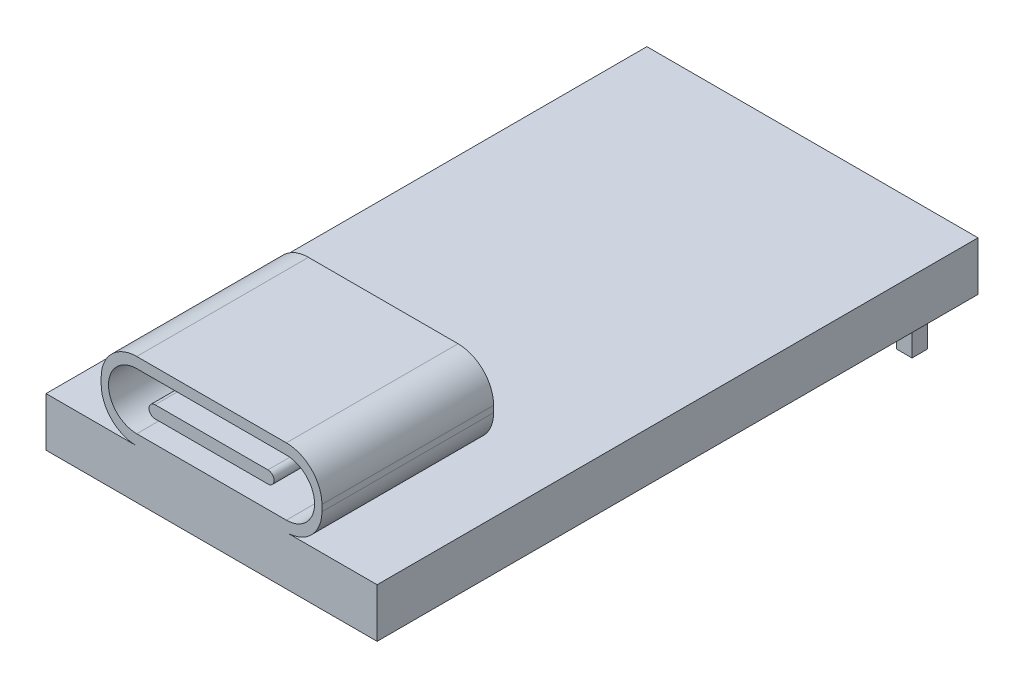
SolidWorks part; units mm, degrees
ref_plane "Front Plane" through (0, 0, 0) normal (0, 0, 1) x (1, 0, 0)
ref_plane "Top Plane" through (0, 0, 0) normal (0, 1, 0) x (1, 0, 0)
ref_plane "Right Plane" through (0, 0, 0) normal (1, 0, 0) x (0, 0, -1)
sketch "Sketch1" plane through (0, 0, 0) normal (0, 1, 0) x (1, 0, 0)
  line L1 (0, 0) -> (13.5, 0)
  line L2 (0, 0) -> (0, 24.5)
  line L3 (0, 24.5) -> (13.5, 24.5)
  line L4 (13.5, 0) -> (13.5, 24.5)
  dimension "D1" = 13.5
  dimension "D2" = 24.5
extrude "Boss-Extrude1" add sketch "Sketch1" along normal blind 2
sketch "Sketch2" plane through (0, 2, 0) normal (0, 1, 0) x (1, 0, 0)
  line L0 (0, 0) -> (13.5, 0) construction
  line L1 (2.25, 0) -> (11.25, 0)
  line L2 (2.25, 0) -> (2.25, 7)
  line L3 (2.25, 7) -> (11.25, 7)
  line L4 (11.25, 0) -> (11.25, 7)
  line L5 (11.25, 3.5) -> (13.5, 3.5) construction
  line L6 (13.5, 0) -> (13.5, 24.5) construction
  line L7 (2.25, 3.5) -> (0, 3.5) construction
  line L8 (0, 24.5) -> (0, 0) construction
  dimension "D1" = 9
  dimension "D2" = 7
extrude "Boss-Extrude2" add sketch "Sketch2" along normal blind 3.16
sketch "Sketch3" plane through (0, 0, 0) normal (0, 0, 1) x (1, 0, 0)
  line L0 (6.75, 5.16) -> (6.75, 3.58) construction
  line L1 (2.25, 5.16) -> (11.25, 5.16) construction
  line L2 (6.75, 3.58) -> (6.75, 2) construction
  line L3 (6.75, 2) -> (9.8, 2)
  line L4 (6.75, 2) -> (3.7, 2)
  line L5 (2.25, 3.45) -> (2.25, 3.71)
  line L6 (2.25, 5.16) -> (2.25, 2) construction
  line L7 (3.7, 5.16) -> (9.8, 5.16)
  line L8 (11.25, 3.71) -> (11.25, 3.45)
  line L9 (9.8, 5.16) -> (11.25, 5.16)
  line L10 (11.25, 5.16) -> (11.25, 3.71)
  line L11 (11.25, 3.45) -> (11.25, 2)
  line L12 (11.25, 2) -> (9.8, 2)
  line L13 (3.7, 2) -> (2.25, 2)
  line L14 (2.25, 2) -> (2.25, 3.45)
  line L15 (2.25, 3.71) -> (2.25, 5.16)
  line L16 (2.25, 5.16) -> (3.7, 5.16)
  arc A0 (11.25, 3.71) -> (9.8, 5.16) centre (9.8, 3.71) ccw
  arc A1 (11.25, 3.45) -> (9.8, 2) centre (9.8, 3.45) cw
  arc A2 (2.25, 3.45) -> (3.7, 2) centre (3.7, 3.45) ccw
  arc A3 (2.25, 3.71) -> (3.7, 5.16) centre (3.7, 3.71) cw
  point P18 (11.25, 5.16)
  point P25 (2.25, 5.16)
  line M6 (11.25, 2) -> (11.25, 5.16)
  line M7 (11.25, 5.16) -> (2.25, 5.16)
  line M8 (2.25, 5.16) -> (2.25, 2)
  dimension "D2" = 1.45
  dimension "D1" = 1.58
extrude "Cut-Extrude1" cut sketch "Sketch3" against normal blind 7.16 contours A2 L13 M8 | A3 M8 M7 | A0 M6 M7 | A1 L12 M6 region at (10.9261, 2.3239, 0) region at (2.5739, 2.3239, 0) region at (10.9261, 4.8361, 0) region at (2.5739, 4.8361, 0)
sketch "Sketch4" plane through (0, 0, 0) normal (0, 0, 1) x (1, 0, 0)
  line L0 (3.7, 5.16) -> (3.7, 2) construction
  line L1 (9.8, 5.16) -> (9.8, 2) construction
  line L2 (3.7, 3.58) -> (9.8, 3.58) construction
  line L3 (3.7, 3.83) -> (9.8, 3.83)
  line L4 (3.7, 3.33) -> (9.8, 3.33)
  line L5 (3.7, 3.58) -> (9.8, 3.58) construction
  line L6 (3.7, 4.73) -> (9.8, 4.73)
  line L7 (3.7, 2.43) -> (9.8, 2.43)
  arc A0 (3.7, 3.83) -> (3.7, 3.33) centre (3.7, 3.58) ccw
  arc A1 (9.8, 3.33) -> (9.8, 3.83) centre (9.8, 3.58) ccw
  arc A2 (3.7, 4.73) -> (3.7, 2.43) centre (3.7, 3.58) ccw
  arc A3 (9.8, 2.43) -> (9.8, 4.73) centre (9.8, 3.58) ccw
  point P7 (6.75, 3.58)
  point P17 (6.75, 3.58)
  dimension "D1" = 0.5
  dimension "D2" = 2.3
extrude "Cut-Extrude2" cut sketch "Sketch4" against normal blind 2.16
sketch "Sketch5" plane through (0, 0, 0) normal (0, 0, 1) x (1, 0, 0)
  line L0 (3.45, 3.58) -> (4.45, 3.58) construction
  line L1 (10.05, 3.58) -> (9.05, 3.58) construction
  line L2 (4.45, 3.58) -> (9.05, 3.58) construction
  line L3 (4.45, 3.83) -> (9.05, 3.83)
  line L4 (4.45, 3.33) -> (9.05, 3.33)
  line L6 (9.8, 3.83) -> (3.7, 3.83) construction
  line L7 (3.7, 3.58) -> (9.8, 3.58) construction
  line L8 (3.7, 3.83) -> (9.8, 3.83)
  line L9 (3.7, 3.33) -> (9.8, 3.33)
  arc A0 (3.7, 3.83) -> (3.7, 3.33) centre (3.7, 3.58) ccw construction
  arc A1 (9.8, 3.33) -> (9.8, 3.83) centre (9.8, 3.58) ccw construction
  arc A2 (4.45, 3.83) -> (4.45, 3.33) centre (4.45, 3.58) ccw
  arc A3 (9.05, 3.33) -> (9.05, 3.83) centre (9.05, 3.58) ccw
  arc A4 (3.7, 3.83) -> (3.7, 3.33) centre (3.7, 3.58) ccw
  arc A5 (9.8, 3.33) -> (9.8, 3.83) centre (9.8, 3.58) ccw
  point P10 (6.75, 3.58)
  point P21 (6.75, 3.58)
  arc M7 (3.7, 3.83) -> (3.7, 3.33) centre (3.7, 3.58) ccw
  line M8 (3.7, 3.33) -> (9.8, 3.33)
  arc M9 (9.8, 3.33) -> (9.8, 3.83) centre (9.8, 3.58) ccw
  line M10 (9.8, 3.83) -> (3.7, 3.83)
  dimension "D1" = 1
extrude "Cut-Extrude3" cut sketch "Sketch5" against normal blind 2.16 contours A2 M10 M7 M8 | A3 M8 M9 M10 region at (3.8787, 3.58, 0) region at (9.6213, 3.58, 0)
sketch "Sketch7" plane through (0, 0, 0) normal (0, -1, 0) x (1, 0, 0)
  line L0 (0, -23.23) -> (1.92, -23.23) construction
  line L1 (0, -24.5) -> (0, 0) construction
  line L2 (13.5, -23.23) -> (11.58, -23.23) construction
  line L3 (13.5, 0) -> (13.5, -24.5) construction
  line L4 (13.5, -24.5) -> (0, -24.5) construction
  line L5 (1.6, -23.55) -> (2.24, -23.55)
  line L6 (1.6, -23.55) -> (1.6, -22.91)
  line L7 (1.6, -22.91) -> (2.24, -22.91)
  line L8 (2.24, -23.55) -> (2.24, -22.91)
  line L9 (1.6, -23.55) -> (2.24, -22.91) construction
  line L10 (1.6, -22.91) -> (2.24, -23.55) construction
  line L11 (0.65, -24.5) -> (3.19, -24.5)
  line L12 (0.65, -24.5) -> (0.65, -21.96)
  line L13 (0.65, -21.96) -> (3.19, -21.96)
  line L14 (3.19, -24.5) -> (3.19, -21.96)
  line L15 (0.65, -24.5) -> (3.19, -21.96) construction
  line L16 (0.65, -21.96) -> (3.19, -24.5) construction
  line L17 (4.78, -23.55) -> (4.78, -22.91)
  line L18 (4.14, -23.55) -> (4.78, -23.55)
  line L19 (4.14, -23.55) -> (4.14, -22.91)
  line L20 (4.14, -22.91) -> (4.78, -22.91)
  line L21 (7.32, -23.55) -> (7.32, -22.91)
  line L22 (6.68, -23.55) -> (7.32, -23.55)
  line L23 (6.68, -23.55) -> (6.68, -22.91)
  line L24 (6.68, -22.91) -> (7.32, -22.91)
  line L25 (9.86, -23.55) -> (9.86, -22.91)
  line L26 (9.22, -23.55) -> (9.86, -23.55)
  line L27 (9.22, -23.55) -> (9.22, -22.91)
  line L28 (9.22, -22.91) -> (9.86, -22.91)
  line L29 (12.08, -22.91) -> (12.08, -23.55) construction
  line L30 (12.08, -23.55) -> (12.08, -23.23) construction
  line L31 (12.08, -23.23) -> (12.4, -23.23) construction
  line L32 (12.4, -23.55) -> (12.4, -22.91)
  line L33 (11.76, -23.55) -> (12.4, -23.55)
  line L34 (11.76, -23.55) -> (11.76, -22.91)
  line L35 (11.76, -22.91) -> (12.4, -22.91)
  dimension "D1" = 0.64
  dimension "D2" = 2.54
  dimension "D4" = 1.92
  dimension "D3" = 5
extrude "Boss-Extrude3" add sketch "Sketch7" along normal blind 2 contours L20 L19 L18 L17 | L24 L23 L22 L21 | L28 L27 L26 L25 | L35 L34 L33 L32 | L8 L7 L6 L5 region at (4.46, 0, -23.23) region at (7, 0, -23.23) region at (9.54, 0, -23.23) region at (12.08, 0, -23.23)
